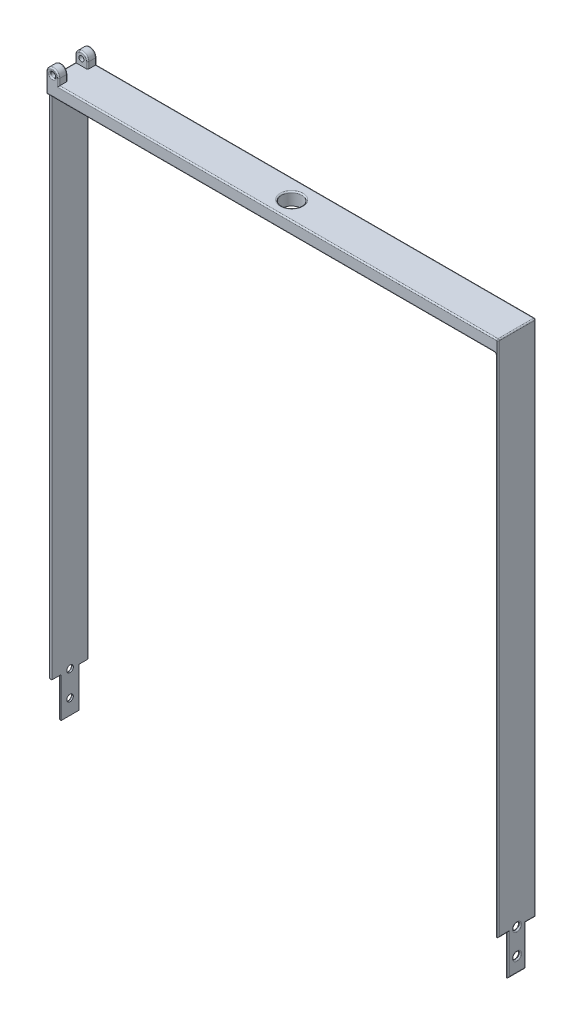
SolidWorks part; units mm, degrees
ref_plane "Front Plane" through (0, 0, 0) normal (0, 0, 1) x (1, 0, 0)
ref_plane "Top Plane" through (0, 0, 0) normal (0, 1, 0) x (1, 0, 0)
ref_plane "Right Plane" through (0, 0, 0) normal (1, 0, 0) x (0, 0, -1)
sketch "Sketch1" plane through (0, 0, 0) normal (0, 0, 1) x (1, 0, 0)
  line L0 (234.297, -112.7002) -> (234.297, 107.2998)
  line L2 (234.297, 107.2998) -> (58.297, 107.2998)
  line L3 (58.297, 107.2998) -> (58.297, -112.7002)
  line L5 (58.297, -112.7002) -> (57.297, -112.7002)
  line L6 (57.297, -112.7002) -> (57.297, 112.2998)
  line L7 (57.297, 112.2998) -> (235.297, 112.2998)
  line L8 (234.297, -112.7002) -> (235.297, -112.7002)
  line L9 (235.297, 112.2998) -> (235.297, -112.7002)
  dimension "D1" = 1
  dimension "D2" = 1
  dimension "D3" = 5
  dimension "D4" = 225
  dimension "D5" = 225
extrude "Boss-Extrude4" add sketch "Sketch1" along normal blind 15
sketch "Sketch5" plane through (57.297, 0, 0) normal (-1, 0, 0) x (0, 0, 1)
  line L0 (7.5, -112.7002) -> (7.5, -102.7002) construction
  line L1 (15, -112.7002) -> (0, -112.7002) construction
  circle A0 centre (7.5, -102.7002) radius 1.3
  circle A1 centre (7.5, -92.7002) radius 1.3
  dimension "D1" = 2.6
  dimension "D3" = 2.6
  dimension "D2" = 10
  dimension "D4" = 10
extrude "Cut-Extrude2" cut sketch "Sketch5" against normal through all both and the other way through all
sketch "Sketch6" plane through (235.297, 0, 0) normal (1, 0, 0) x (0, 0, -1)
  line L0 (-15, -92.9262) -> (-11, -92.9262)
  line L1 (-15, -112.7002) -> (-15, 112.2998) construction
  line L2 (-11, -92.9262) -> (-11, -108.7002)
  line L3 (-11, -108.7002) -> (-4, -108.7002)
  line L4 (-4, -108.7002) -> (-4, -92.9262)
  line L5 (-4, -92.9262) -> (0, -92.9262)
  line L6 (0, -112.7002) -> (0, 112.2998) construction
  line L7 (0, -92.9262) -> (0, -112.7002)
  line L8 (0, -112.7002) -> (-15, -112.7002)
  line L9 (-15, -112.7002) -> (-15, -92.9262)
  dimension "D1" = 4
  dimension "D2" = 4
  dimension "D3" = 4
extrude "Cut-Extrude4" cut sketch "Sketch6" against normal through all both and the other way through all
fillet "Fillet1" radius 0.5 35 edges at (146.297, 107.2998, 15) (57.297, -108.7002, 7.5) (57.297, -100.8132, 4) (57.297, -92.9262, 2) (57.297, 112.2998, 7.5) (57.297, 9.6868, 15) (57.297, -92.9262, 13) (57.297, -100.8132, 11) (57.297, -102.7002, 6.2) (57.297, -92.7002, 6.2) (234.297, -108.7002, 7.5) (234.297, -100.8132, 4) (234.297, -92.9262, 2) (234.297, 107.2998, 7.5) (234.297, 7.1868, 15) (234.297, -92.9262, 13) (234.297, -100.8132, 11) (234.297, -102.7002, 6.2) (234.297, -92.7002, 6.2) (58.297, 7.1868, 0) (146.297, 107.2998, 0) (234.297, 7.1868, 0) (146.297, 112.2998, 0) (57.297, 9.6868, 0) (57.797, -92.9262, 0) (235.297, 112.2998, 7.5) (235.297, 9.6868, 0) (235.297, -92.9262, 2) (235.297, -100.8132, 4) (235.297, -108.7002, 7.5) (235.297, -100.8132, 11) (235.297, -92.9262, 13) (235.297, 9.6868, 15) (235.297, -102.7002, 8.8) (235.297, -92.7002, 8.8)
sketch "Sketch8" plane through (0, 112.2998, 0) normal (0, 1, 0) x (1, 0, 0)
  line L0 (146.297, 0) -> (146.297, -24.872) construction
  line L1 (57.797, 0) -> (234.797, 0) construction
  line L2 (57.797, -7.75) -> (159.0912, -7.75) construction
  line L3 (57.797, -0.5) -> (57.797, -15) construction
  circle A0 centre (146.297, -7.75) radius 5
  dimension "D1" = 10
extrude "Cut-Extrude5" cut sketch "Sketch8" against normal through all
fillet "Fillet2" radius 0.5 7 edges at (57.4435, -92.7798, 14.8536) (235.1506, 112.1534, 14.8536) (57.4435, 112.1534, 14.8536) (58.297, 7.4368, 15) (58.047, -92.9262, 15) (146.297, 112.2998, 15) (146.297, 112.2998, 12.75)
sketch "Sketch9" plane through (0, 112.2998, 0) normal (0, 1, 0) x (1, 0, 0)
  circle A0 centre (146.297, -7.75) radius 6.4894
  circle A1 centre (146.297, -7.75) radius 4
extrude "Boss-Extrude5" add sketch "Sketch9" against normal blind 5 contours A1 | A0
fillet "Fillet3" radius 0.5 1 edges at (146.297, 112.2998, 11.75)
sketch "Sketch11" plane through (0, 112.2998, 0) normal (0, 1, 0) x (1, 0, 0)
  line L0 (146.297, -7.75) -> (146.297, 5.5828) construction
  line L1 (146.297, -7.75) -> (42.8628, -7.75) construction
  line L2 (56.297, 6.3991) -> (56.297, -20.3098) construction
  line L3 (234.797, -15) -> (57.797, -15) construction
  line L4 (56.297, 0) -> (61.297, 0)
  line L5 (56.297, 0) -> (56.297, -15)
  line L6 (56.297, -15) -> (61.297, -15)
  line L7 (61.297, 0) -> (61.297, -15)
  dimension "D1" = 90
  dimension "D2" = 5
extrude "Boss-Extrude6" add sketch "Sketch11" along normal blind 5 and the other way blind 5
sketch "Sketch15" plane through (0, 0, 0) normal (0, 0, -1) x (-1, 0, 0)
  line L0 (-56.297, 107.2998) -> (-56.297, 117.2998) construction
  line L1 (-61.297, 117.2998) -> (-56.297, 117.2998) construction
  line L3 (-61.297, 117.2998) -> (-56.297, 117.2998)
  line L4 (-61.297, 117.2998) -> (-61.297, 114.7998)
  line L5 (-61.297, 114.7998) -> (-56.297, 114.7998)
  line L6 (-56.297, 117.2998) -> (-56.297, 114.7998)
  circle A0 centre (-58.797, 114.7998) radius 2.5
  circle A1 centre (-58.797, 114.7998) radius 1
  dimension "D1" = 2.5
  dimension "D2" = 2.5
extrude "Cut-Extrude8" cut sketch "Sketch15" against normal blind 15 contours L5 A1 | L5 A1 | A0 L3 | A0 L5 L6
sketch "Sketch16" plane through (0, 112.2998, 0) normal (0, 1, 0) x (1, 0, 0)
  line L0 (61.297, -0.5) -> (61.297, -14.5) construction
  line L1 (61.297, -3.5) -> (56.297, -3.5)
  line L2 (61.297, -3.5) -> (61.297, -11.5)
  line L3 (61.297, -11.5) -> (56.297, -11.5)
  line L4 (56.297, -3.5) -> (56.297, -11.5)
  line L5 (56.297, -15) -> (56.297, 0) construction
  line L6 (61.297, 0) -> (56.297, 0) construction
  dimension "D1" = 3.5
  dimension "D2" = 8
extrude "Cut-Extrude9" cut sketch "Sketch16" along normal blind 7
fillet "Fillet4" radius 0.5 20 edges at (61.297, 113.5498, 11.5) (58.797, 117.2998, 11.5) (61.297, 113.5498, 3.5) (58.797, 117.2998, 3.5) (57.047, 107.2998, 0) (59.547, 107.2998, 15) (59.547, 107.2998, 0) (61.297, 113.2998, 0) (58.797, 117.2998, 15) (58.797, 117.2998, 0) (57.797, 114.7998, 15) (57.797, 114.7998, 0) (56.297, 113.5498, 11.5) (56.297, 107.2998, 7.5) (56.297, 111.0498, 0) (56.297, 113.5498, 3.5) (56.297, 112.2998, 7.5) (61.297, 113.2998, 15) (57.047, 107.2998, 15) (56.297, 111.0498, 15)
